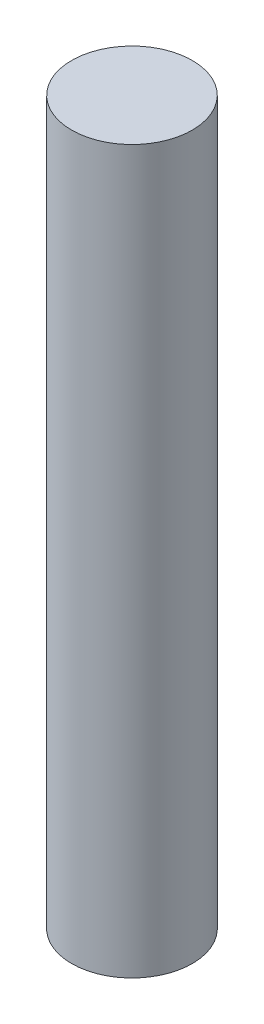
SolidWorks part; units mm, degrees
ref_plane "Front Plane" through (0, 0, 0) normal (0, 0, 1) x (1, 0, 0)
ref_plane "Top Plane" through (0, 0, 0) normal (0, 1, 0) x (1, 0, 0)
ref_plane "Right Plane" through (0, 0, 0) normal (1, 0, 0) x (0, 0, -1)
sketch "Sketch1" plane through (0, 0, 0) normal (0, 1, 0) x (1, 0, 0)
  circle A0 centre (0, 0) radius 2.065
  dimension "D1" = 4.13
extrude "Boss-Extrude1" add sketch "Sketch1" along normal blind 24.7
ref_plane "Midplane" through (0, 12.35, 0) normal (0, -1, 0) x (-1, 0, 0)
ref_plane "Min compression for click" through (0, 18.7, 0) normal (0, 1, 0) x (1, 0, 0)
sketch "Min compression and tube ID" plane through (0, 18.7, 0) normal (0, 1, 0) x (1, 0, 0)
  circle A0 centre (0, 0) radius 2.065 construction
  circle A1 centre (0, 0) radius 2.065
  circle A2 centre (0, 0) radius 2.265
  dimension "D2" = 4.53
  dimension "D1" = 0.2
ref_axis "Axis1" through (0, 24.7, 0) along (0, -1, 0)
equation "\"spring_tube_clearance\" = 0.2"
equation "\"D1@Min compression and tube ID\"=\"spring_tube_clearance\""
